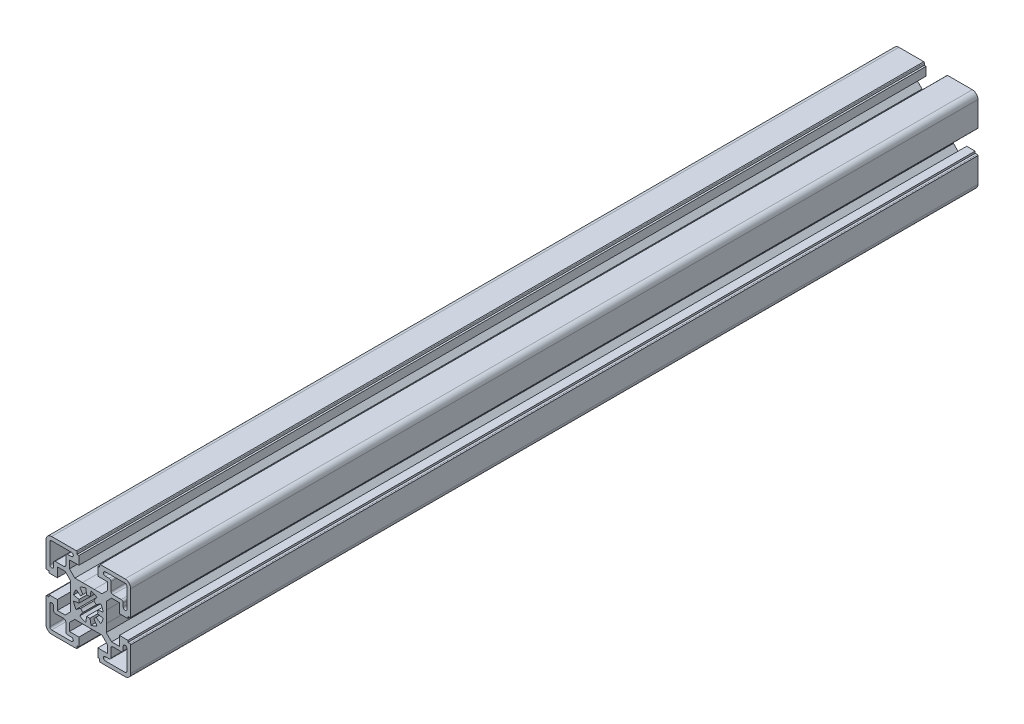
SolidWorks part; units mm, degrees
ref_plane "Front Plane" through (0, 0, 0) normal (0, 0, 1) x (1, 0, 0)
ref_plane "Top Plane" through (0, 0, 0) normal (0, 1, 0) x (1, 0, 0)
ref_plane "Right Plane" through (0, 0, 0) normal (1, 0, 0) x (0, 0, -1)
sketch "Sketch1" plane through (0, 0, 0) normal (0, 0, 1) x (1, 0, 0)
  line L0 (0, 34.901) -> (0, -38.8683) construction
  line L1 (-27.7848, -31.1091) -> (42.6814, -31.1091) construction
  line L3 (-0.8682, 4.924) -> (-1.3892, 7.8785)
  line L4 (-4.5886, 6.5532) -> (-2.8679, 4.0957)
  line L5 (-4.0957, 2.8679) -> (-6.5532, 4.5886)
  line L6 (-7.8784, 1.3892) -> (-4.924, 0.8682)
  line L10 (4.924, 0.8682) -> (7.8785, 1.3892)
  line L12 (6.5532, 4.5886) -> (4.0957, 2.8679)
  line L30 (-9.5, 3.1227) -> (-9.5, 7.207)
  line L31 (-9.5, 7.207) -> (-12.3429, 10.0499)
  line L32 (-12.3429, 10.0499) -> (-16.5, 10.0499)
  line L33 (-16.5, 10.0499) -> (-16.5, 4.9999)
  line L34 (-16.5, 4.9999) -> (-20.9999, 4.9999)
  line L35 (-20.9999, 4.9999) -> (-20.9999, 6)
  line L36 (-20.9999, 6) -> (-21.9999, 6)
  line L37 (-22.4999, 6.2999) -> (-22.4999, 19.5)
  line L38 (-19.4999, 22.5) -> (-6.3, 22.5)
  line L39 (-6, 21.9999) -> (-6, 20.9999)
  line L40 (-6, 20.9999) -> (-5, 20.9999)
  line L41 (-5, 20.9999) -> (-5, 16.5)
  line L42 (-5, 16.5) -> (-10.0501, 16.5)
  line L43 (-10.0501, 16.5) -> (-10.0501, 12.3428)
  line L44 (-10.0501, 12.3428) -> (-7.2071, 9.4999)
  line L45 (-7.2071, 9.4999) -> (-3.1228, 9.4999)
  line L82 (2.8679, 4.0957) -> (4.5886, 6.5532)
  line L83 (1.3892, 7.8784) -> (0.8682, 4.924)
  line L85 (3.1227, 9.5) -> (7.207, 9.5)
  line L86 (7.207, 9.5) -> (10.0499, 12.3429)
  line L87 (10.0499, 12.3429) -> (10.0499, 16.5)
  line L94 (-17.5001, 12) -> (-13.0001, 12)
  line L95 (-12.0001, 13) -> (-12.0001, 17.4999)
  line L96 (-11.0001, 18.4999) -> (-9.0001, 18.4999)
  line L97 (-19.5001, 20.5) -> (-9.0001, 20.5)
  line L98 (-20.5001, 8.9999) -> (-20.5001, 19.5)
  line L99 (-18.5001, 8.9999) -> (-18.5001, 11)
  line L101 (10.0499, 16.5) -> (4.9999, 16.5)
  line L102 (4.9999, 16.5) -> (4.9999, 20.9999)
  line L103 (4.9999, 20.9999) -> (6, 20.9999)
  line L104 (6, 20.9999) -> (6, 21.9999)
  line L105 (6.2999, 22.4999) -> (19.5, 22.4999)
  line L110 (22.5, 19.4999) -> (22.5, 6.3)
  line L111 (21.9999, 6) -> (20.9999, 6)
  line L118 (-3.1228, 9.4999) -> (3.1227, 9.5)
  line L119 (20.9999, 6) -> (20.9999, 5)
  line L124 (20.9999, 5) -> (16.5, 5)
  line L125 (16.5, 5) -> (16.5, 10.0501)
  line L126 (16.5, 10.0501) -> (12.3428, 10.0501)
  line L127 (12.3428, 10.0501) -> (9.4999, 7.2071)
  line L128 (9.4999, 7.2071) -> (9.4999, 3.1228)
  line L129 (12, 17.5001) -> (12, 13.0001)
  line L130 (13, 12.0001) -> (17.4999, 12.0001)
  line L131 (18.4999, 11.0001) -> (18.4999, 9.0001)
  line L132 (20.5, 19.5001) -> (20.5, 9.0001)
  line L133 (8.9999, 20.5001) -> (19.5, 20.5001)
  line L134 (8.9999, 18.5001) -> (11, 18.5001)
  line L135 (-9.5, 3.1227) -> (-9.4999, -3.1228)
  line L136 (9.4999, 3.1228) -> (9.5, -3.1227)
  line L137 (3.1228, -9.4999) -> (-3.1227, -9.5)
  line L138 (-0.8682, 4.924) -> (-1.3892, 7.8785)
  line L147 (0.8682, -4.924) -> (1.3892, -7.8785)
  line L148 (4.5886, -6.5532) -> (2.8679, -4.0957)
  line L149 (-4.924, -0.8682) -> (-7.8785, -1.3892)
  line L154 (4.0957, -2.8679) -> (6.5532, -4.5886)
  line L155 (7.8784, -1.3892) -> (4.924, -0.8682)
  line L157 (9.5, -3.1227) -> (9.5, -7.207)
  line L158 (9.5, -7.207) -> (12.3429, -10.0499)
  line L159 (12.3429, -10.0499) -> (16.5, -10.0499)
  line L160 (16.5, -10.0499) -> (16.5, -4.9999)
  line L161 (16.5, -4.9999) -> (20.9999, -4.9999)
  line L162 (20.9999, -4.9999) -> (20.9999, -6)
  line L163 (20.9999, -6) -> (21.9999, -6)
  line L164 (22.4999, -6.2999) -> (22.4999, -19.5)
  line L165 (19.4999, -22.5) -> (6.3, -22.5)
  line L166 (6, -21.9999) -> (6, -20.9999)
  line L167 (6, -20.9999) -> (5, -20.9999)
  line L168 (5, -20.9999) -> (5, -16.5)
  line L169 (5, -16.5) -> (10.0501, -16.5)
  line L176 (10.0501, -16.5) -> (10.0501, -12.3428)
  line L178 (4.924, 0.8682) -> (7.8785, 1.3892) [skipped]
  line L179 (6.5532, 4.5886) -> (4.0957, 2.8679) [skipped]
  line L180 (2.8679, 4.0957) -> (4.5886, 6.5532) [skipped]
  line L181 (1.3892, 7.8784) -> (0.8682, 4.924) [skipped]
  line L183 (3.1227, 9.5) -> (7.207, 9.5) [skipped]
  line L184 (7.207, 9.5) -> (10.0499, 12.3429) [skipped]
  line L185 (10.0499, 12.3429) -> (10.0499, 16.5) [skipped]
  line L186 (10.0499, 16.5) -> (4.9999, 16.5) [skipped]
  line L187 (4.9999, 16.5) -> (4.9999, 20.9999) [skipped]
  line L188 (4.9999, 20.9999) -> (6, 20.9999) [skipped]
  line L189 (6, 20.9999) -> (6, 21.9999) [skipped]
  line L190 (6.2999, 22.4999) -> (19.5, 22.4999) [skipped]
  line L191 (22.5, 19.4999) -> (22.5, 6.3) [skipped]
  line L192 (21.9999, 6) -> (20.9999, 6) [skipped]
  line L193 (20.9999, 6) -> (20.9999, 5) [skipped]
  line L194 (20.9999, 5) -> (16.5, 5) [skipped]
  line L195 (16.5, 5) -> (16.5, 10.0501) [skipped]
  line L196 (16.5, 10.0501) -> (12.3428, 10.0501) [skipped]
  line L197 (12.3428, 10.0501) -> (9.4999, 7.2071) [skipped]
  line L198 (9.4999, 7.2071) -> (9.4999, 3.1228) [skipped]
  line L199 (12, 17.5001) -> (12, 13.0001) [skipped]
  line L200 (13, 12.0001) -> (17.4999, 12.0001) [skipped]
  line L201 (18.4999, 11.0001) -> (18.4999, 9.0001) [skipped]
  line L202 (20.5, 19.5001) -> (20.5, 9.0001) [skipped]
  line L203 (8.9999, 20.5001) -> (19.5, 20.5001) [skipped]
  line L204 (8.9999, 18.5001) -> (11, 18.5001) [skipped]
  line L206 (0.8682, -4.924) -> (1.3892, -7.8785) [skipped]
  line L207 (4.5886, -6.5532) -> (2.8679, -4.0957) [skipped]
  line L208 (4.0957, -2.8679) -> (6.5532, -4.5886) [skipped]
  line L209 (7.8784, -1.3892) -> (4.924, -0.8682) [skipped]
  line L210 (9.5, -3.1227) -> (9.5, -7.207) [skipped]
  line L211 (9.5, -7.207) -> (12.3429, -10.0499) [skipped]
  line L212 (12.3429, -10.0499) -> (16.5, -10.0499) [skipped]
  line L213 (16.5, -10.0499) -> (16.5, -4.9999) [skipped]
  line L214 (16.5, -4.9999) -> (20.9999, -4.9999) [skipped]
  line L215 (20.9999, -4.9999) -> (20.9999, -6) [skipped]
  line L216 (20.9999, -6) -> (21.9999, -6) [skipped]
  line L217 (22.4999, -6.2999) -> (22.4999, -19.5) [skipped]
  line L218 (19.4999, -22.5) -> (6.3, -22.5) [skipped]
  line L219 (6, -21.9999) -> (6, -20.9999) [skipped]
  line L220 (6, -20.9999) -> (5, -20.9999) [skipped]
  line L221 (5, -20.9999) -> (5, -16.5) [skipped]
  line L222 (5, -16.5) -> (10.0501, -16.5) [skipped]
  line L223 (10.0501, -16.5) -> (10.0501, -12.3428) [skipped]
  line L224 (10.0501, -12.3428) -> (7.2071, -9.4999) [skipped]
  line L225 (7.2071, -9.4999) -> (3.1228, -9.4999) [skipped]
  line L226 (17.5001, -12) -> (13.0001, -12) [skipped]
  line L227 (12.0001, -13) -> (12.0001, -17.4999) [skipped]
  line L228 (11.0001, -18.4999) -> (9.0001, -18.4999) [skipped]
  line L229 (19.5001, -20.5) -> (9.0001, -20.5) [skipped]
  line L230 (20.5001, -8.9999) -> (20.5001, -19.5) [skipped]
  line L231 (18.5001, -8.9999) -> (18.5001, -11) [skipped]
  line L235 (-6.5532, -4.5886) -> (-4.0957, -2.8679) [skipped]
  line L236 (-2.8679, -4.0957) -> (-4.5886, -6.5532) [skipped]
  line L237 (-1.3892, -7.8784) -> (-0.8682, -4.924) [skipped]
  line L238 (-3.1227, -9.5) -> (-7.207, -9.5) [skipped]
  line L239 (-7.207, -9.5) -> (-10.0499, -12.3429) [skipped]
  line L240 (-10.0499, -12.3429) -> (-10.0499, -16.5) [skipped]
  line L241 (-10.0499, -16.5) -> (-4.9999, -16.5) [skipped]
  line L242 (-4.9999, -16.5) -> (-4.9999, -20.9999) [skipped]
  line L243 (-4.9999, -20.9999) -> (-6, -20.9999) [skipped]
  line L244 (-6, -20.9999) -> (-6, -21.9999) [skipped]
  line L245 (-6.2999, -22.4999) -> (-19.5, -22.4999) [skipped]
  line L246 (-22.5, -19.4999) -> (-22.5, -6.3) [skipped]
  line L247 (-21.9999, -6) -> (-20.9999, -6) [skipped]
  line L248 (-20.9999, -6) -> (-20.9999, -5) [skipped]
  line L249 (-20.9999, -5) -> (-16.5, -5) [skipped]
  line L250 (-16.5, -5) -> (-16.5, -10.0501) [skipped]
  line L251 (-16.5, -10.0501) -> (-12.3428, -10.0501) [skipped]
  line L252 (-12.3428, -10.0501) -> (-9.4999, -7.2071) [skipped]
  line L253 (-9.4999, -7.2071) -> (-9.4999, -3.1228) [skipped]
  line L254 (-12, -17.5001) -> (-12, -13.0001) [skipped]
  line L255 (-13, -12.0001) -> (-17.4999, -12.0001) [skipped]
  line L256 (-18.4999, -11.0001) -> (-18.4999, -9.0001) [skipped]
  line L257 (-20.5, -19.5001) -> (-20.5, -9.0001) [skipped]
  line L258 (-8.9999, -20.5001) -> (-19.5, -20.5001) [skipped]
  line L259 (-8.9999, -18.5001) -> (-11, -18.5001) [skipped]
  line L261 (10.0501, -12.3428) -> (7.2071, -9.4999)
  line L262 (7.2071, -9.4999) -> (3.1228, -9.4999)
  line L263 (17.5001, -12) -> (13.0001, -12)
  line L264 (12.0001, -13) -> (12.0001, -17.4999)
  line L265 (11.0001, -18.4999) -> (9.0001, -18.4999)
  line L266 (19.5001, -20.5) -> (9.0001, -20.5)
  line L267 (20.5001, -8.9999) -> (20.5001, -19.5)
  line L268 (18.5001, -8.9999) -> (18.5001, -11)
  line L272 (4.924, 0.8682) -> (7.8785, 1.3892)
  line L275 (-4.924, -0.8682) -> (-7.8785, -1.3892)
  line L276 (-6.5532, -4.5886) -> (-4.0957, -2.8679)
  line L277 (-2.8679, -4.0957) -> (-4.5886, -6.5532)
  line L278 (-1.3892, -7.8784) -> (-0.8682, -4.924)
  line L280 (-3.1227, -9.5) -> (-7.207, -9.5)
  line L281 (-7.207, -9.5) -> (-10.0499, -12.3429)
  line L282 (-10.0499, -12.3429) -> (-10.0499, -16.5)
  line L283 (-10.0499, -16.5) -> (-4.9999, -16.5)
  line L284 (-4.9999, -16.5) -> (-4.9999, -20.9999)
  line L285 (-4.9999, -20.9999) -> (-6, -20.9999)
  line L286 (-6, -20.9999) -> (-6, -21.9999)
  line L287 (-6.2999, -22.4999) -> (-19.5, -22.4999)
  line L288 (-22.5, -19.4999) -> (-22.5, -6.3)
  line L289 (-21.9999, -6) -> (-20.9999, -6)
  line L290 (-20.9999, -6) -> (-20.9999, -5)
  line L291 (-20.9999, -5) -> (-16.5, -5)
  line L292 (-16.5, -5) -> (-16.5, -10.0501)
  line L293 (-16.5, -10.0501) -> (-12.3428, -10.0501)
  line L294 (-12.3428, -10.0501) -> (-9.4999, -7.2071)
  line L295 (-9.4999, -7.2071) -> (-9.4999, -3.1228)
  line L296 (-12, -17.5001) -> (-12, -13.0001)
  line L297 (-13, -12.0001) -> (-17.4999, -12.0001)
  line L298 (-18.4999, -11.0001) -> (-18.4999, -9.0001)
  line L299 (-20.5, -19.5001) -> (-20.5, -9.0001)
  line L300 (-8.9999, -20.5001) -> (-19.5, -20.5001)
  line L301 (-8.9999, -18.5001) -> (-11, -18.5001)
  line L305 (0.8682, -4.924) -> (1.3892, -7.8785)
  arc A1 (-1.3892, 7.8785) -> (-4.5886, 6.5532) centre (0, 0) ccw
  arc A2 (-2.8679, 4.0957) -> (-4.0957, 2.8679) centre (0, 0) ccw
  arc A3 (-6.5532, 4.5886) -> (-7.8784, 1.3892) centre (0, 0) ccw
  arc A4 (-4.924, 0.8682) -> (-4.924, -0.8682) centre (0, 0) ccw
  arc A7 (0.8682, 4.924) -> (-0.8682, 4.924) centre (0, 0) ccw
  arc A8 (7.8785, 1.3892) -> (6.5532, 4.5886) centre (0, 0) ccw
  arc A20 (-22.4999, 6.2999) -> (-21.9999, 6) centre (-22.041, 6.4983) ccw
  arc A21 (-19.4999, 22.5) -> (-22.4999, 19.5) centre (-19.4999, 19.5) ccw
  arc A22 (-6, 21.9999) -> (-6.3, 22.5) centre (-6.4984, 22.041) ccw
  arc A32 (4.0957, 2.8679) -> (2.8679, 4.0957) centre (0, 0) ccw
  arc A33 (4.5886, 6.5532) -> (1.3892, 7.8784) centre (0, 0) ccw
  arc A44 (-17.5001, 12) -> (-18.5001, 11) centre (-17.5001, 11) ccw
  arc A45 (-13.0001, 12) -> (-12.0001, 13) centre (-13.0001, 13) ccw
  arc A46 (-11.0001, 18.4999) -> (-12.0001, 17.4999) centre (-11.0001, 17.4999) ccw
  arc A47 (-9.0001, 18.4999) -> (-9.0001, 20.5) centre (-9.0001, 19.5) ccw
  arc A48 (-19.5001, 20.5) -> (-20.5001, 19.5) centre (-19.5001, 19.5) ccw
  arc A49 (-20.5001, 8.9999) -> (-18.5001, 8.9999) centre (-19.5001, 8.9999) ccw
  arc A51 (0.8682, 4.924) -> (-0.8682, 4.924) centre (0, 0) ccw
  arc A52 (4.924, -0.8682) -> (4.924, 0.8682) centre (0, 0) ccw
  arc A53 (6.2999, 22.4999) -> (6, 21.9999) centre (6.4983, 22.041) ccw
  arc A60 (-7.8785, -1.3892) -> (-6.5532, -4.5886) centre (0, 0) ccw
  arc A64 (22.5, 19.4999) -> (19.5, 22.4999) centre (19.5, 19.4999) ccw
  arc A65 (21.9999, 6) -> (22.5, 6.3) centre (22.041, 6.4984) ccw
  arc A66 (12, 17.5001) -> (11, 18.5001) centre (11, 17.5001) ccw
  arc A73 (7.8785, 1.3892) -> (6.5532, 4.5886) centre (0, 0) ccw [skipped]
  arc A74 (4.0957, 2.8679) -> (2.8679, 4.0957) centre (0, 0) ccw [skipped]
  arc A75 (4.5886, 6.5532) -> (1.3892, 7.8784) centre (0, 0) ccw [skipped]
  arc A76 (6.2999, 22.4999) -> (6, 21.9999) centre (6.4983, 22.041) ccw [skipped]
  arc A77 (22.5, 19.4999) -> (19.5, 22.4999) centre (19.5, 19.4999) ccw [skipped]
  arc A78 (21.9999, 6) -> (22.5, 6.3) centre (22.041, 6.4984) ccw [skipped]
  arc A79 (12, 17.5001) -> (11, 18.5001) centre (11, 17.5001) ccw [skipped]
  arc A80 (12, 13.0001) -> (13, 12.0001) centre (13, 13.0001) ccw [skipped]
  arc A81 (18.4999, 11.0001) -> (17.4999, 12.0001) centre (17.4999, 11.0001) ccw [skipped]
  arc A82 (18.4999, 9.0001) -> (20.5, 9.0001) centre (19.5, 9.0001) ccw [skipped]
  arc A83 (20.5, 19.5001) -> (19.5, 20.5001) centre (19.5, 19.5001) ccw [skipped]
  arc A84 (8.9999, 20.5001) -> (8.9999, 18.5001) centre (8.9999, 19.5001) ccw [skipped]
  arc A85 (1.3892, -7.8785) -> (4.5886, -6.5532) centre (0, 0) ccw [skipped]
  arc A86 (2.8679, -4.0957) -> (4.0957, -2.8679) centre (0, 0) ccw [skipped]
  arc A87 (6.5532, -4.5886) -> (7.8784, -1.3892) centre (0, 0) ccw [skipped]
  arc A88 (4.924, -0.8682) -> (4.924, 0.8682) centre (0, 0) ccw [skipped]
  arc A89 (22.4999, -6.2999) -> (21.9999, -6) centre (22.041, -6.4983) ccw [skipped]
  arc A90 (19.4999, -22.5) -> (22.4999, -19.5) centre (19.4999, -19.5) ccw [skipped]
  arc A91 (6, -21.9999) -> (6.3, -22.5) centre (6.4984, -22.041) ccw [skipped]
  arc A92 (17.5001, -12) -> (18.5001, -11) centre (17.5001, -11) ccw [skipped]
  arc A93 (13.0001, -12) -> (12.0001, -13) centre (13.0001, -13) ccw [skipped]
  arc A94 (11.0001, -18.4999) -> (12.0001, -17.4999) centre (11.0001, -17.4999) ccw [skipped]
  arc A95 (9.0001, -18.4999) -> (9.0001, -20.5) centre (9.0001, -19.5) ccw [skipped]
  arc A96 (19.5001, -20.5) -> (20.5001, -19.5) centre (19.5001, -19.5) ccw [skipped]
  arc A97 (20.5001, -8.9999) -> (18.5001, -8.9999) centre (19.5001, -8.9999) ccw [skipped]
  arc A98 (-4.0957, -2.8679) -> (-2.8679, -4.0957) centre (0, 0) ccw [skipped]
  arc A99 (-4.5886, -6.5532) -> (-1.3892, -7.8784) centre (0, 0) ccw [skipped]
  arc A100 (-0.8682, -4.924) -> (0.8682, -4.924) centre (0, 0) ccw [skipped]
  arc A101 (-6.2999, -22.4999) -> (-6, -21.9999) centre (-6.4983, -22.041) ccw [skipped]
  arc A102 (-22.5, -19.4999) -> (-19.5, -22.4999) centre (-19.5, -19.4999) ccw [skipped]
  arc A103 (-21.9999, -6) -> (-22.5, -6.3) centre (-22.041, -6.4984) ccw [skipped]
  arc A104 (-12, -17.5001) -> (-11, -18.5001) centre (-11, -17.5001) ccw [skipped]
  arc A105 (-12, -13.0001) -> (-13, -12.0001) centre (-13, -13.0001) ccw [skipped]
  arc A106 (-18.4999, -11.0001) -> (-17.4999, -12.0001) centre (-17.4999, -11.0001) ccw [skipped]
  arc A107 (-18.4999, -9.0001) -> (-20.5, -9.0001) centre (-19.5, -9.0001) ccw [skipped]
  arc A108 (-20.5, -19.5001) -> (-19.5, -20.5001) centre (-19.5, -19.5001) ccw [skipped]
  arc A109 (-8.9999, -20.5001) -> (-8.9999, -18.5001) centre (-8.9999, -19.5001) ccw [skipped]
  arc A110 (12, 13.0001) -> (13, 12.0001) centre (13, 13.0001) ccw
  arc A111 (18.4999, 11.0001) -> (17.4999, 12.0001) centre (17.4999, 11.0001) ccw
  arc A112 (18.4999, 9.0001) -> (20.5, 9.0001) centre (19.5, 9.0001) ccw
  arc A113 (20.5, 19.5001) -> (19.5, 20.5001) centre (19.5, 19.5001) ccw
  arc A114 (8.9999, 20.5001) -> (8.9999, 18.5001) centre (8.9999, 19.5001) ccw
  arc A115 (-1.3892, 7.8785) -> (-4.5886, 6.5532) centre (0, 0) ccw
  arc A116 (1.3892, -7.8785) -> (4.5886, -6.5532) centre (0, 0) ccw
  arc A117 (2.8679, -4.0957) -> (4.0957, -2.8679) centre (0, 0) ccw
  arc A118 (6.5532, -4.5886) -> (7.8784, -1.3892) centre (0, 0) ccw
  arc A119 (4.924, -0.8682) -> (4.924, 0.8682) centre (0, 0) ccw
  arc A120 (-0.8682, -4.924) -> (0.8682, -4.924) centre (0, 0) ccw
  arc A121 (22.4999, -6.2999) -> (21.9999, -6) centre (22.041, -6.4983) ccw
  arc A122 (19.4999, -22.5) -> (22.4999, -19.5) centre (19.4999, -19.5) ccw
  arc A123 (6, -21.9999) -> (6.3, -22.5) centre (6.4984, -22.041) ccw
  arc A124 (17.5001, -12) -> (18.5001, -11) centre (17.5001, -11) ccw
  arc A125 (13.0001, -12) -> (12.0001, -13) centre (13.0001, -13) ccw
  arc A126 (11.0001, -18.4999) -> (12.0001, -17.4999) centre (11.0001, -17.4999) ccw
  arc A127 (9.0001, -18.4999) -> (9.0001, -20.5) centre (9.0001, -19.5) ccw
  arc A128 (19.5001, -20.5) -> (20.5001, -19.5) centre (19.5001, -19.5) ccw
  arc A129 (20.5001, -8.9999) -> (18.5001, -8.9999) centre (19.5001, -8.9999) ccw
  arc A130 (7.8785, 1.3892) -> (6.5532, 4.5886) centre (0, 0) ccw
  arc A131 (-7.8785, -1.3892) -> (-6.5532, -4.5886) centre (0, 0) ccw
  arc A132 (-4.0957, -2.8679) -> (-2.8679, -4.0957) centre (0, 0) ccw
  arc A133 (-4.5886, -6.5532) -> (-1.3892, -7.8784) centre (0, 0) ccw
  arc A134 (-0.8682, -4.924) -> (0.8682, -4.924) centre (0, 0) ccw
  arc A135 (-4.924, 0.8682) -> (-4.924, -0.8682) centre (0, 0) ccw
  arc A136 (-6.2999, -22.4999) -> (-6, -21.9999) centre (-6.4983, -22.041) ccw
  arc A137 (-22.5, -19.4999) -> (-19.5, -22.4999) centre (-19.5, -19.4999) ccw
  arc A138 (-21.9999, -6) -> (-22.5, -6.3) centre (-22.041, -6.4984) ccw
  arc A139 (-12, -17.5001) -> (-11, -18.5001) centre (-11, -17.5001) ccw
  arc A140 (-12, -13.0001) -> (-13, -12.0001) centre (-13, -13.0001) ccw
  arc A141 (-18.4999, -11.0001) -> (-17.4999, -12.0001) centre (-17.4999, -11.0001) ccw
  arc A142 (-18.4999, -9.0001) -> (-20.5, -9.0001) centre (-19.5, -9.0001) ccw
  arc A143 (-20.5, -19.5001) -> (-19.5, -20.5001) centre (-19.5, -19.5001) ccw
  arc A144 (-8.9999, -20.5001) -> (-8.9999, -18.5001) centre (-8.9999, -19.5001) ccw
  arc A145 (1.3892, -7.8785) -> (4.5886, -6.5532) centre (0, 0) ccw
  point P528 (0, 0)
  dimension "D1" = 4
  dimension "D2" = 4
extrude "Boss-Extrude1" add sketch "Sketch1" along normal blind 450 contours L277 A131 L101 L169 L45 L44 L43 L42 L41 L40 L39 A22 L38 A21 L37 A20 L36 L35 L34 L33 region at (-8.8636, 5.1649, 0)
